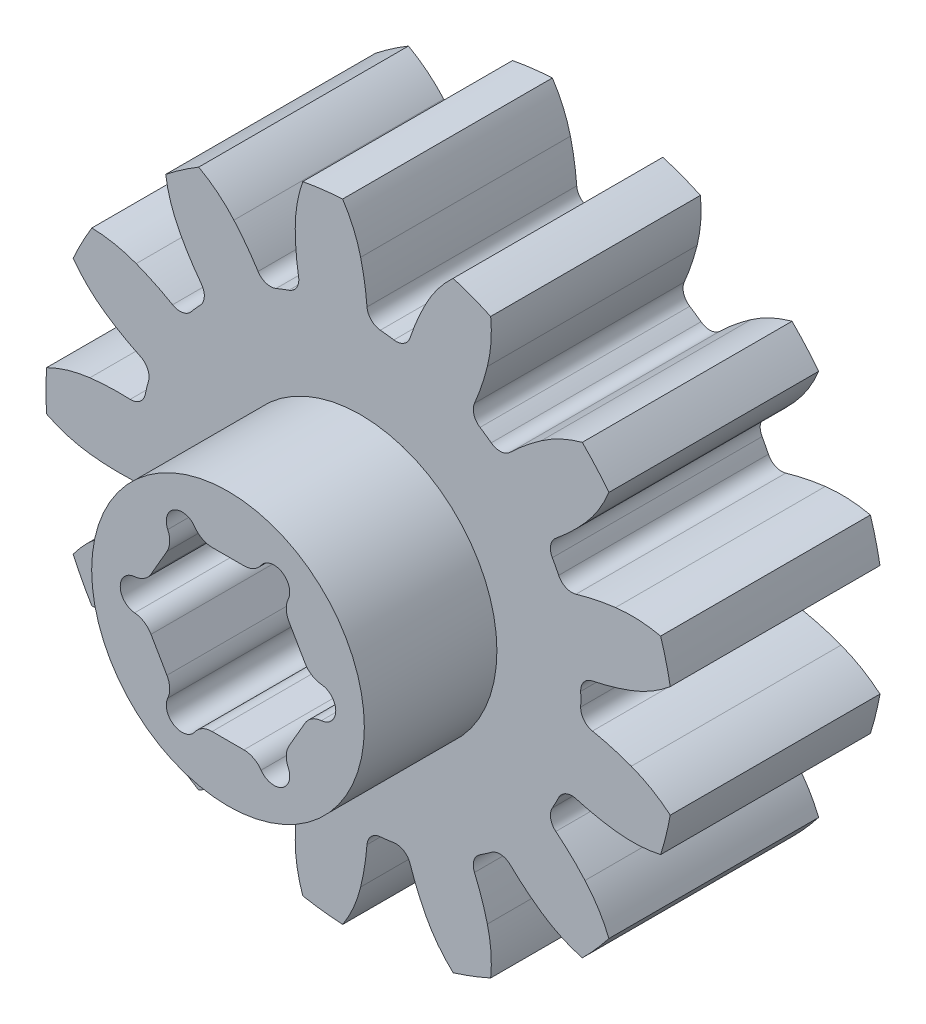
SolidWorks part; units mm, degrees
material "PLA/ABS"
ref_plane "Front" through (0, 0, 0) normal (0, 0, 1) x (1, 0, 0)
ref_plane "Top" through (0, 0, 0) normal (0, 1, 0) x (1, 0, 0)
ref_plane "Right" through (0, 0, 0) normal (1, 0, 0) x (0, 0, -1)
sketch "Sketch1" plane through (0, 0, 0) normal (0, 0, 1) x (1, 0, 0)
  line L0 (0, 0) -> (8.255, 0) construction
  line L1 (8.255, 0) -> (9.525, 0) construction
  circle A0 centre (0, 0) radius 8.255 construction
  circle A1 centre (0, 0) radius 9.525
  dimension "D1" = 16.51
  dimension "D2" = 1.27
extrude "Round Stock" add sketch "Sketch1" along normal mid plane 6.35
sketch "Sketch2" plane through (0, 0, 3.175) normal (0, 0, 1) x (1, 0, 0)
  line L0 (0, 0) -> (6.6675, 0) construction
  line L1 (6.6675, 0) -> (8.255, 0) construction
  line L2 (0, 0) -> (-9.525, 0) construction
  line L3 (0, 0) -> (-8.434, -4.4265) construction
  line L4 (-8.6992, -3.8793) -> (-7.7195, -2.9249) construction
  line L5 (-7.7195, -2.9249) -> (-6.3199, -2.1249) construction
  line L6 (-9.5056, -0.6078) -> (-8.1945, -0.9976) construction
  line L7 (-8.1945, -0.9976) -> (-6.5834, -1.0555) construction
  line L8 (-7.2559, -3.8082) -> (-7.7195, -2.9249) construction
  line L9 (-8.1945, -0.9976) -> (-8.1945, 0) construction
  line L12 (0, 0) -> (-8.1945, -0.9976) construction
  line L13 (0, 0) -> (-7.7195, -2.9249) construction
  line L14 (-7.7195, -2.9249) -> (-6.0358, -7.3685) construction
  line L15 (-8.1945, -0.9976) -> (-8.7688, 3.7195) construction
  line L16 (-7.7195, -2.9249) -> (-8.1945, -0.9976) construction
  line L17 (-6.4738, -1.5956) -> (-6.5834, -1.0555) construction
  line L18 (-6.4738, -1.5956) -> (-6.3199, -2.1249) construction
  circle A0 centre (0, 0) radius 8.255 construction
  circle A1 centre (0, 0) radius 6.6675 construction
  circle A2 centre (0, 0) radius 9.525 construction
  arc A3 (-8.6992, -3.8793) -> (-9.5056, -0.6078) centre (0, 0) cw
  arc A4 (-6.3199, -2.1249) -> (-6.5834, -1.0555) centre (0, 0) cw construction
  arc A6 (-8.6992, -3.8793) -> (-7.7195, -2.9249) centre (-5.4661, -6.218) cw
  arc A7 (-9.5056, -0.6078) -> (-8.1945, -0.9976) centre (-7.7296, 2.9656) ccw
  arc A8 (-7.7195, -2.9249) -> (-6.6596, -2.3175) centre (-3.3876, -9.2555) cw
  arc A9 (-8.1945, -0.9976) -> (-6.9738, -1.0428) centre (-7.3008, 6.621) ccw
  arc A10 (-6.6596, -2.3175) -> (-6.4211, -1.7957) centre (-6.8492, -1.9154) ccw
  arc A11 (-6.9738, -1.0428) -> (-6.5201, -1.394) centre (-6.9548, -1.4869) cw
  arc A12 (-6.4211, -1.7957) -> (-6.5201, -1.394) centre (0, 0) cw
  dimension "D6" = 16.51
  dimension "D9" = 0.4445
  dimension "D12" = 3.9903
  dimension "D2" = 1.5875
  dimension "D3" = 27.692
  dimension "D4" = 0.9976
  dimension "D5" = 0.9976
  dimension "D11" = 1.985
  dimension "D8" = 14.5
  dimension "D7" = 14.5
  dimension "D14" = 9
  dimension "D15" = 9
extrude "Single Tooth" cut sketch "Sketch2" against normal through all
ref_axis "Axis" through (0, 0, 50) along (0, 0, -1)
pattern_circular "Tooth Pattern" count 13 over 360 about axis through (0, 0, 50) along (0, 0, -1) of "Single Tooth"
sketch "Sketch4" plane through (0, 0, 3.175) normal (0, 0, 1) x (1, 0, 0)
  circle A0 centre (0, 0) radius 3.1039
  dimension "D1" = 6.2078
extrude "TopBearingBoss" [suppressed] add sketch "Sketch4" along normal blind 0.635
mirror "BottomBearingBoss" [suppressed] about plane through (0, 0, 0) normal (0, 0, 1)
sketch "Sketch6" [suppressed] plane through (0, 0, 0) normal (0, 0, 1) x (1, 0, 0)
  line L1 (1.4005, 2.4257) -> (-1.4005, 2.4257)
  line L2 (-1.4005, 2.4257) -> (-2.801, 0)
  line L3 (-2.801, 0) -> (-1.4005, -2.4257)
  line L4 (-1.4005, -2.4257) -> (1.4005, -2.4257)
  line L5 (1.4005, -2.4257) -> (2.801, 0)
  line L6 (2.801, 0) -> (1.4005, 2.4257)
  circle A0 centre (0, 0) radius 2.4257 construction
  circle A1 centre (0, 0) radius 2.4257 construction
extrude "Hex" [suppressed] cut sketch "Sketch6" against normal through all both and the other way through all
sketch "Sketch7" plane through (0, 0, -3.175) normal (0, 0, -1) x (-1, 0, 0)
  line L1 (1.3931, -2.413) -> (2.7863, 0)
  line L2 (2.7863, 0) -> (1.3931, 2.413)
  line L3 (1.3931, 2.413) -> (-1.3931, 2.413)
  line L4 (-1.3931, 2.413) -> (-2.7863, 0)
  line L5 (-2.7863, 0) -> (-1.3931, -2.413)
  line L6 (-1.3931, -2.413) -> (1.3931, -2.413)
  circle A0 centre (0, 0) radius 2.413 construction
  dimension "D1" = 4.826
extrude "Cut-Extrude1" cut sketch "Sketch7" against normal through all
sketch "Sketch8" plane through (0, 0, 3.175) normal (0, 0, 1) x (1, 0, 0)
  line L6 (-1.3931, -2.413) -> (1.3931, -2.413)
  line L7 (-2.7863, 0) -> (-1.3931, -2.413)
  line L8 (-1.3931, 2.413) -> (-2.7863, 0)
  line L9 (1.3931, 2.413) -> (-1.3931, 2.413)
  line L10 (2.7863, 0) -> (1.3931, 2.413)
  line L11 (1.3931, -2.413) -> (2.7863, 0)
  line L12 (-1.3931, -2.413) -> (1.3931, -2.413)
  line L13 (-2.7863, 0) -> (-1.3931, -2.413)
  line L14 (-1.3931, 2.413) -> (-2.7863, 0)
  line L15 (1.3931, 2.413) -> (-1.3931, 2.413)
  line L16 (2.7863, 0) -> (1.3931, 2.413)
  line L17 (1.3931, -2.413) -> (2.7863, 0)
  circle A0 centre (0, 0) radius 4.1275
  dimension "D2" = 8.255
  dimension "D1" = 0
extrude "Boss-Extrude1" add sketch "Sketch8" along normal blind 4.0132
sketch "Sketch9" plane through (0, 0, -3.175) normal (0, 0, -1) x (-1, 0, 0)
  line L0 (0, 4.318) -> (0, 4.1275) construction
  line L1 (2.493, -4.318) -> (4.986, 0)
  line L2 (4.986, 0) -> (2.493, 4.318)
  line L3 (2.493, 4.318) -> (-2.493, 4.318)
  line L4 (-2.493, 4.318) -> (-4.986, 0)
  line L5 (-4.986, 0) -> (-2.493, -4.318)
  line L6 (-2.493, -4.318) -> (2.493, -4.318)
  circle A0 centre (0, 0) radius 4.318 construction
  circle A3 centre (0, 0) radius 4.1275 construction
  point P1 (0, 0)
  dimension "D1" = 0.1905
extrude "Cut-Extrude2" cut sketch "Sketch9" against normal blind 3.302
fillet "Fillet1" radius 0.635 6 edges at (4.986, 0, -1.524) (2.493, -4.318, -1.524) (-2.493, -4.318, -1.524) (-4.986, 0, -1.524) (-2.493, 4.318, -1.524) (2.493, 4.318, -1.524)
sketch "Sketch10" plane through (0, 0, 7.1882) normal (0, 0, 1) x (1, 0, 0)
  circle A0 centre (-1.3931, 2.413) radius 0.4762
  circle A1 centre (1.3931, 2.413) radius 0.4763
  circle A2 centre (2.7863, 0) radius 0.4763
  circle A3 centre (1.3931, -2.413) radius 0.4763
  circle A4 centre (-1.3931, -2.413) radius 0.4762
  circle A5 centre (-2.7863, 0) radius 0.4763
  dimension "D1" = 0.9525
extrude "Cut-Extrude3" cut sketch "Sketch10" against normal through all
fillet "Fillet2" radius 0.635 12 edges at (0.9169, -2.413, 3.6576) (-0.9169, -2.413, 3.6576) (-1.6313, -2.0006, 3.6576) (-2.5482, -0.4124, 3.6576) (-2.5482, 0.4124, 3.6576) (-1.6313, 2.0006, 3.6576) (-0.9169, 2.413, 3.6576) (0.9169, 2.413, 3.6576) (1.6313, 2.0006, 3.6576) (2.5482, 0.4124, 3.6576) (2.5482, -0.4124, 3.6576) (1.6313, -2.0006, 3.6576)
equation "\"N_teeth\"= \"No_Teeth\""
equation "\"pitch_diameter\"= \"N_teeth\" / \"Pitch\""
equation "\"Pd\"=\"N_teeth\"/\"pitch_diameter\""
equation "\"addendum\"=1.000/\"Pd\""
equation "\"face_width\"=0.25"
equation "\"deddendum\"=1.250/\"Pd\""
equation "\"D3@Sketch2\" = 360/\"N_teeth\""
equation "\"tooth_thickness\"=1.571/\"Pd\""
equation "\"D4@Sketch2\" = \"tooth_thickness\"/2"
equation "\"D5@Sketch2\" = \"tooth_thickness\"/2"
equation "\"Pressure_Angle\"= iif ( \"Pitch\" = 20 , 14.500000 , iif ( \"Pitch\" = 32 , 20 , 20 ) )"
equation "\"base_fillet\"=0.35/\"Pd\""
equation "\"D12@Sketch2\" = 2*\"tooth_thickness\""
equation "\"hub_projection\"=0.250000"
equation "\"sss_diam\"= 0.062500"
equation "\"D1@Sketch1\"=\"pitch_diameter\""
equation "\"D2@Sketch1\"=\"addendum\""
equation "\"D1@Round Stock\" = \"face_width\""
equation "\"D2@Sketch2\"=\"deddendum\""
equation "\"D6@Sketch2\"=\"pitch_diameter\""
equation "\"D7@Sketch2\"=\"Pressure_Angle\""
equation "\"D8@Sketch2\"=\"D7@Sketch2\""
equation "\"D9@Sketch2\"=\"base_fillet\""
equation "\"D1@Tooth Pattern\" = \"N_teeth\""
equation "\"Pitch\"= \"GearPitch\""
equation "\"BossDia\"= \"BoreDia\" * 1.3"
equation "\"Hex\"= iif ( \"HexBore\" = 1 , \"unsuppressed\" , \"suppressed\" )"
equation "\"TopBearingBoss\" = iif ( \"Bearing_Boss\" = 0 , \"suppressed\" , \"unsuppressed\" )"
equation "\"BottomBearingBoss\"= iif ( \"Bearing_Boss\" > 1 , \"unsuppressed\" , \"suppressed\" )"
equation "\"D1@Sketch4\"=\"BossDia\""
equation "\"ToothCount\"= iif ( \"No_Teeth\" < 22 , \"suppressed\" , \"unsuppressed\" )"
